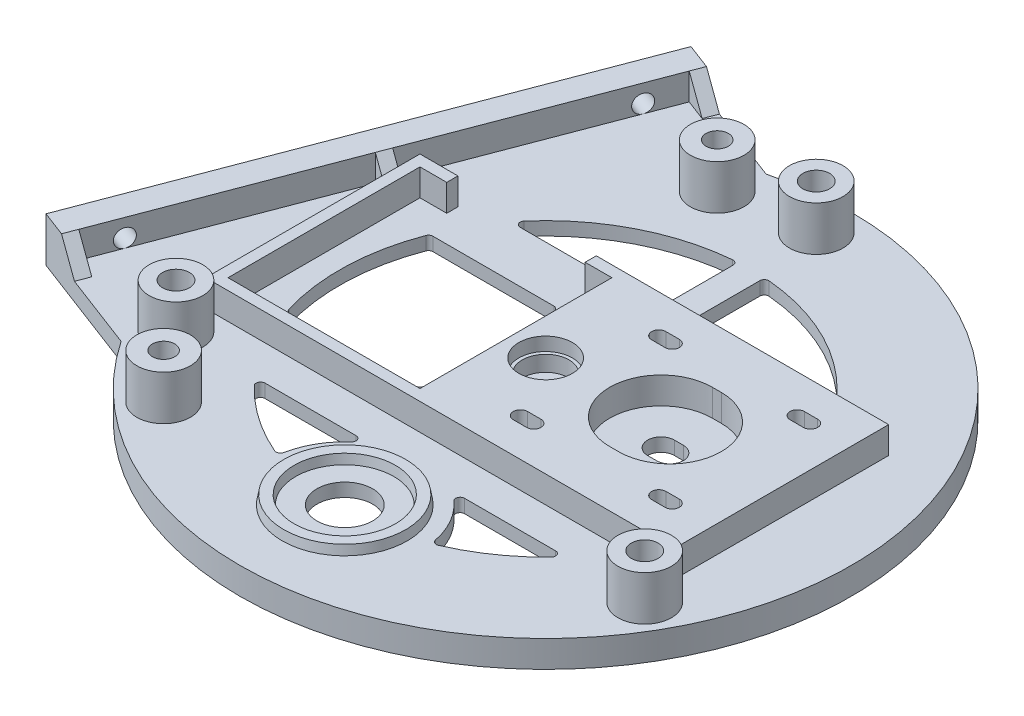
SolidWorks part; units mm, degrees
material "ABS"
ref_plane "Front Plane" through (0, 0, 0) normal (0, 0, 1) x (1, 0, 0)
ref_plane "Top Plane" through (0, 0, 0) normal (0, 1, 0) x (1, 0, 0)
ref_plane "Right Plane" through (0, 0, 0) normal (1, 0, 0) x (0, 0, -1)
sketch "Sketch1" plane through (0, 0, 0) normal (0, 0, 1) x (1, 0, 0)
  line L0 (0, 0) -> (68.5, 0)
  line L1 (68.5, 0) -> (68.5, -6)
  line L2 (68.5, -6) -> (66.5, -6)
  line L3 (66.5, -6) -> (66.5, -3)
  line L5 (53.5, -3) -> (53.5, -6)
  line L6 (53.5, -6) -> (50.5, -6)
  line L7 (50.5, -6) -> (50.5, -3)
  line L8 (50.5, -3) -> (8, -3)
  line L9 (8, -3) -> (8, -8)
  line L10 (8, -8) -> (0, -8)
  line L11 (0, -8) -> (0, 0)
  line L12 (62.3516, -3) -> (66.5, -3)
  line L13 (57.6484, -3) -> (53.5, -3)
  arc A0 (62.3516, -3) -> (57.6484, -3) centre (60, -6.6) ccw
  point P4 (67.5, -6)
  dimension "D2" = 4.3
  dimension "D1" = 60
  dimension "D3" = 6.5
  dimension "D4" = 3
  dimension "D5" = 6.5
  dimension "D6" = 3
  dimension "D7" = 2
  dimension "D8" = 50.5
  dimension "D9" = 0.6
  dimension "D10" = 8
  dimension "D11" = 8
revolve "Revolve1" add sketch "Sketch1" angle 360 about L11
sketch "Sketch2" plane through (0, 0, 0) normal (0, 1, 0) x (1, 0, 0)
  line L0 (-52.5, -30.3109) -> (0, 60.6218) construction
  line L1 (0, 60.6218) -> (52.5, -30.3109) construction
  line L2 (52.5, -30.3109) -> (-52.5, -30.3109) construction
  line L3 (0, 0) -> (0, 60.6218) construction
  line L4 (0, 0) -> (52.5, -30.3109) construction
  line L5 (0, 0) -> (-52.5, -30.3109) construction
  line L6 (0, 0) -> (0, -45) construction
  line L7 (-40.2731, -45.3109) -> (-40.2731, -30.3109) construction
  line L8 (-19.1038, 57.533) -> (-6.1134, 50.033) construction
  circle A0 centre (0, 60.6218) radius 6
  circle A1 centre (0, 60.6218) radius 3
  circle A2 centre (52.5, -30.3109) radius 6
  circle A3 centre (-52.5, -30.3109) radius 6
  circle A4 centre (-52.5, -30.3109) radius 3
  circle A5 centre (52.5, -30.3109) radius 3
  circle A6 centre (0, -45) radius 6.25 construction
  arc A7 (0, 60.6218) -> (-24.7136, -55.3555) centre (0, 0) ccw construction
  circle A8 centre (-40.2731, -45.3109) radius 6
  circle A9 centre (-19.1038, 57.533) radius 6
  circle A10 centre (-40.2731, -45.3109) radius 2.5
  circle A11 centre (-19.1038, 57.533) radius 2.5
  arc A12 (15.6635, -19.9954) -> (14.3368, 20.9671) centre (0, 0) ccw construction
  dimension "D2" = 12
  dimension "D3" = 6
  dimension "D5" = 12.5
  dimension "D6" = 12
  dimension "D8" = 5
  dimension "D9" = 25.4
  dimension "D1" = 105
  dimension "D4" = 45
  dimension "D7" = 15
extrude "Boss-Extrude1" add sketch "Sketch2" along normal blind 10
sketch "Sketch3" plane through (0, 0, 0) normal (0, 1, 0) x (1, 0, 0)
  circle A0 centre (0, -45) radius 6.25
  circle A1 centre (0, -45) radius 6.25 construction
extrude "Cut-Extrude1" cut sketch "Sketch3" against normal blind 10
sketch "Sketch12" plane through (0, 0, 0) normal (0, 1, 0) x (1, 0, 0)
  line L0 (0, 60.6218) -> (-40.2731, -45.3109) construction
  line L1 (-56.7747, -38.326) -> (-83.9292, -28.0025)
  line L2 (-83.9292, -28.0025) -> (-44.1287, 76.6871)
  line L3 (-44.1287, 76.6871) -> (-16.9742, 66.3636)
  line L4 (0, 0) -> (-64.0289, 24.3423) construction
  circle A0 centre (0, 0) radius 68.5 construction
  arc A1 (-56.7747, -38.326) -> (-16.9742, 66.3636) centre (0, 0) cw
  point P8 (-20.1366, 7.6554)
  dimension "D2" = 68.5
  dimension "D1" = 112
extrude "Boss-Extrude5" add sketch "Sketch12" against normal blind 4 contours L2 A1 L3 | L1 A1 L2 region at (-41.1369, 0, -61.2808) region at (-71.4581, 0, 18.4748)
sketch "Sketch4" plane through (0, 0, 0) normal (0, 1, 0) x (1, 0, 0)
  circle A0 centre (0, -45) radius 11
  circle A1 centre (0, -45) radius 14
  dimension "D1" = 22
  dimension "D2" = 28
extrude "Boss-Extrude2" add sketch "Sketch4" along normal blind 2 draft 10
sketch "Sketch5" plane through (0, 0, 0) normal (0, 1, 0) x (1, 0, 0)
  line L0 (51.3563, -22.5103) -> (51.3563, 25.4897)
  line L1 (51.3563, -22.5103) -> (-53.6437, -22.5103)
  line L2 (51.3563, 25.4897) -> (-53.6437, 25.4897) construction
  line L3 (-53.6437, -22.5103) -> (-53.6437, 25.4897)
  line L4 (-51.1437, 22.9897) -> (-45.1437, 22.9897)
  line L5 (-53.6437, 1.4897) -> (51.3563, 1.4897) construction
  line L6 (25.3563, 1.4897) -> (25.3563, 25.4897) construction
  line L7 (26.3563, 1.4897) -> (24.3563, 1.4897) construction
  line L8 (26.3563, -10.0103) -> (24.3563, -10.0103)
  line L9 (26.3563, 12.9897) -> (24.3563, 12.9897)
  line L10 (-45.1437, 22.9897) -> (-45.1437, 25.4897)
  line L11 (-51.1437, -20.0103) -> (-51.1437, 22.9897)
  line L12 (-51.1437, 22.9897) -> (-8.1437, 22.9897) construction
  line L13 (-8.1437, 22.9897) -> (-8.1437, -20.0103)
  line L14 (-8.1437, -20.0103) -> (-51.1437, -20.0103)
  line L15 (-45.1437, 25.4897) -> (-53.6437, 25.4897)
  line L16 (-8.1437, 22.9897) -> (-14.1437, 22.9897)
  line L17 (-14.1437, 22.9897) -> (-14.1437, 25.4897)
  line L18 (-14.1437, 25.4897) -> (51.3563, 25.4897)
  line L19 (-38.5203, 74.5549) -> (-78.3208, -30.1347)
  line L20 (-44.1287, 76.6871) -> (-16.9742, 66.3636) construction
  line L21 (-56.7747, -38.326) -> (-83.9292, -28.0025) construction
  line L22 (-78.3208, -30.1347) -> (-83.9292, -28.0025)
  line L23 (-83.9292, -28.0025) -> (-44.1287, 76.6871)
  line L24 (-83.9292, -28.0025) -> (-44.1287, 76.6871) construction
  line L25 (-44.1287, 76.6871) -> (-38.5203, 74.5549)
  arc A1 (26.3563, -10.0103) -> (26.3563, 12.9897) centre (26.3563, 1.4897) ccw
  arc A2 (24.3563, 12.9897) -> (24.3563, -10.0103) centre (24.3563, 1.4897) ccw
  arc A3 (15.6635, -19.9954) -> (14.3368, 20.9671) centre (0, 0) ccw construction
  point P10 (25.3563, 1.4897)
  point P18 (-8.1437, 1.4897)
  dimension "D3" = 23
  dimension "D1" = 48
  dimension "D2" = 105
  dimension "D4" = 2
  dimension "D5" = 26
  dimension "D6" = 2.5
  dimension "D7" = 43
  dimension "D8" = 43
  dimension "D9" = 6
  dimension "D10" = 6
  dimension "D11" = 6
extrude "Boss-Extrude3" add sketch "Sketch5" along normal blind 6
sketch "Sketch6" plane through (0, 6, 0) normal (0, 1, 0) x (1, 0, 0)
  line L0 (40.8563, -14.0103) -> (40.8563, 16.9897) construction
  line L1 (40.8563, -14.0103) -> (9.8563, -14.0103) construction
  line L2 (40.8563, 16.9897) -> (9.8563, 16.9897) construction
  line L3 (9.8563, -14.0103) -> (9.8563, 16.9897) construction
  line L4 (40.8563, -14.0103) -> (9.8563, 16.9897) construction
  line L5 (40.8563, 16.9897) -> (9.8563, -14.0103) construction
  line L6 (25.3563, 1.4897) -> (25.3563, 25.4897) construction
  line L7 (11.3563, -14.0103) -> (8.3563, -14.0103) construction
  line L8 (11.3563, -15.6103) -> (8.3563, -15.6103)
  line L9 (11.3563, -12.4103) -> (8.3563, -12.4103)
  line L10 (42.3563, -14.0103) -> (39.3563, -14.0103) construction
  line L11 (42.3563, -15.6103) -> (39.3563, -15.6103)
  line L12 (42.3563, -12.4103) -> (39.3563, -12.4103)
  line L13 (42.3563, 16.9897) -> (39.3563, 16.9897) construction
  line L14 (42.3563, 15.3897) -> (39.3563, 15.3897)
  line L15 (42.3563, 18.5897) -> (39.3563, 18.5897)
  line L16 (11.3563, 16.9897) -> (8.3563, 16.9897) construction
  line L17 (11.3563, 15.3897) -> (8.3563, 15.3897)
  line L18 (11.3563, 18.5897) -> (8.3563, 18.5897)
  arc A0 (11.3563, -15.6103) -> (11.3563, -12.4103) centre (11.3563, -14.0103) ccw
  arc A1 (8.3563, -12.4103) -> (8.3563, -15.6103) centre (8.3563, -14.0103) ccw
  arc A2 (42.3563, -15.6103) -> (42.3563, -12.4103) centre (42.3563, -14.0103) ccw
  arc A3 (39.3563, -12.4103) -> (39.3563, -15.6103) centre (39.3563, -14.0103) ccw
  arc A4 (42.3563, 15.3897) -> (42.3563, 18.5897) centre (42.3563, 16.9897) ccw
  arc A5 (39.3563, 18.5897) -> (39.3563, 15.3897) centre (39.3563, 16.9897) ccw
  arc A6 (11.3563, 15.3897) -> (11.3563, 18.5897) centre (11.3563, 16.9897) ccw
  arc A7 (8.3563, 18.5897) -> (8.3563, 15.3897) centre (8.3563, 16.9897) ccw
  point P1 (25.3563, 1.4897)
  point P2 (25.3563, 16.9897)
  point P11 (9.8563, -14.0103)
  point P21 (40.8563, -14.0103)
  point P28 (40.8563, 16.9897)
  point P35 (9.8563, 16.9897)
  dimension "D2" = 1.6
  dimension "D1" = 31
  dimension "D3" = 3
  dimension "D4" = 2
  dimension "D5" = 2
extrude "Cut-Extrude2" cut sketch "Sketch6" against normal through all
sketch "Sketch7" plane through (0, 0, 0) normal (0, 1, 0) x (1, 0, 0)
  line L0 (26.3563, 1.4897) -> (24.3563, 1.4897) construction
  line L1 (26.3563, -1.5103) -> (24.3563, -1.5103)
  line L2 (26.3563, 4.4897) -> (24.3563, 4.4897)
  arc A0 (26.3563, -1.5103) -> (26.3563, 4.4897) centre (26.3563, 1.4897) ccw
  arc A1 (24.3563, 4.4897) -> (24.3563, -1.5103) centre (24.3563, 1.4897) ccw
  point P2 (25.3563, 1.4897)
  dimension "D1" = 3
extrude "Cut-Extrude3" cut sketch "Sketch7" against normal through all
sketch "Sketch8" plane through (0, 6, 0) normal (0, 1, 0) x (1, 0, 0)
  circle A0 centre (0, 0) radius 1.75
  dimension "D1" = 3.5
extrude "Cut-Extrude4" cut sketch "Sketch8" against normal through all
chamfer "Chamfer1" distance 2 angle 45 16 edges at (37.7563, -3, 14.0103) (40.8563, -3, 12.4103) (40.8563, -3, 15.6103) (43.9563, -3, 14.0103) (37.7563, -3, -16.9897) (40.8563, -3, -18.5897) (40.8563, -3, -15.3897) (43.9563, -3, -16.9897) (6.7563, -3, -16.9897) (9.8563, -3, -18.5897) (9.8563, -3, -15.3897) (12.9563, -3, -16.9897) (6.7563, -3, 14.0103) (9.8563, -3, 12.4103) (9.8563, -3, 15.6103) (12.9563, -3, 14.0103)
sketch "Sketch9" plane through (0, 6, 0) normal (0, 1, 0) x (1, 0, 0)
  circle A0 centre (0, 0) radius 5.25
  dimension "D1" = 10.5
extrude "Cut-Extrude5" cut sketch "Sketch9" against normal blind 6.5
sketch "Sketch10" plane through (0, 6, 0) normal (0, 1, 0) x (1, 0, 0)
  circle A0 centre (0, 0) radius 6
  dimension "D1" = 12
extrude "Cut-Extrude6" cut sketch "Sketch10" against normal blind 3
sketch "Sketch11" plane through (0, 0, 0) normal (0, 1, 0) x (1, 0, 0)
  line L0 (-14.1437, -13.0103) -> (-14.1437, 15.9897)
  line L1 (-15.1437, 16.9897) -> (-42.2431, 16.9897)
  line L2 (-15.1437, -14.0103) -> (-43.2536, -14.0103)
  line L3 (-8.1437, 22.9897) -> (-8.1437, -20.0103) construction
  line L4 (-8.1437, -20.0103) -> (-51.1437, -20.0103) construction
  line L5 (-51.1437, 22.9897) -> (-8.1437, 22.9897) construction
  line L6 (-36.3293, 28.4897) -> (36.3293, 28.4897) construction
  line L7 (51.3563, 25.4897) -> (-53.6437, 25.4897) construction
  line L8 (3, 29.4897) -> (3, 44.9905)
  line L9 (-3, 29.4897) -> (-3, 44.9905)
  line L10 (-34.2126, 28.4897) -> (-4, 28.4897)
  line L11 (4, 28.4897) -> (34.2126, 28.4897)
  line L12 (52.5, -30.3109) -> (-52.5, -30.3109) construction
  line L13 (-32.5542, -30.3109) -> (-12.1463, -30.3109)
  line L14 (12.1463, -30.3109) -> (32.5542, -30.3109)
  arc A0 (-43.1783, 16.3437) -> (-44.2113, -13.2984) centre (0, 0) ccw
  arc A1 (-36.3293, 28.4897) -> (36.3293, 28.4897) centre (0, 0) cw construction
  arc A2 (-4.0886, 45.9866) -> (-34.9701, 30.1426) centre (0, 0) ccw
  arc A3 (34.9701, 30.1426) -> (4.0886, 45.9866) centre (0, 0) ccw
  arc A4 (33.2749, -32.0041) -> (18.3502, -42.3645) centre (0, 0) cw
  arc A5 (-18.3502, -42.3645) -> (-33.2749, -32.0041) centre (0, 0) cw
  arc A6 (16.9717, -41.6411) -> (11.4826, -32.0589) centre (0, -45) ccw
  arc A7 (-16.9717, -41.6411) -> (-11.4826, -32.0589) centre (0, -45) cw
  arc A8 (33.2749, -32.0041) -> (32.5542, -30.3109) centre (32.5542, -31.3109) ccw
  arc A9 (-33.2749, -32.0041) -> (-32.5542, -30.3109) centre (-32.5542, -31.3109) cw
  arc A10 (18.3502, -42.3645) -> (16.9717, -41.6411) centre (17.9527, -41.4469) cw
  arc A11 (-18.3502, -42.3645) -> (-16.9717, -41.6411) centre (-17.9527, -41.4469) ccw
  arc A12 (11.4826, -32.0589) -> (12.1463, -30.3109) centre (12.1463, -31.3109) cw
  arc A13 (-11.4826, -32.0589) -> (-12.1463, -30.3109) centre (-12.1463, -31.3109) ccw
  arc A14 (-14.1437, -13.0103) -> (-15.1437, -14.0103) centre (-15.1437, -13.0103) cw
  arc A15 (-14.1437, 15.9897) -> (-15.1437, 16.9897) centre (-15.1437, 15.9897) ccw
  arc A16 (3, 29.4897) -> (4, 28.4897) centre (4, 29.4897) ccw
  arc A17 (-3, 29.4897) -> (-4, 28.4897) centre (-4, 29.4897) cw
  arc A18 (-43.2536, -14.0103) -> (-44.2113, -13.2984) centre (-43.2536, -13.0103) cw
  arc A19 (-42.2431, 16.9897) -> (-43.1783, 16.3437) centre (-42.2431, 15.9897) ccw
  arc A20 (34.2126, 28.4897) -> (34.9701, 30.1426) centre (34.2126, 29.4897) ccw
  arc A21 (3, 44.9905) -> (4.0886, 45.9866) centre (4, 44.9905) cw
  arc A22 (-3, 44.9905) -> (-4.0886, 45.9866) centre (-4, 44.9905) ccw
  arc A23 (-34.2126, 28.4897) -> (-34.9701, 30.1426) centre (-34.2126, 29.4897) cw
  point P37 (34.8243, -30.3109)
  point P40 (-34.8243, -30.3109)
  point P47 (9.1407, -30.3109)
  point P50 (-9.1407, -30.3109)
  point P57 (3, 28.4897)
  point P60 (-3, 28.4897)
  point P70 (3, 46.0704)
  point P73 (-3, 46.0704)
  dimension "D4" = 3
  dimension "D5" = 6
  dimension "D6" = 1
  dimension "D1" = 6
  dimension "D2" = 6
  dimension "D3" = 6
extrude "Cut-Extrude7" cut sketch "Sketch11" against normal through all
sketch "Sketch13" plane through (-64.0289, 0, -24.3423) normal (-0.9347, 0, -0.3554) x (-0.3554, 0, 0.9347)
  line L0 (0, -4) -> (-56, -4) construction
  line L1 (-56, -4) -> (-56, 6) construction
  line L2 (56, -4) -> (56, 6) construction
  circle A0 centre (-45, 2) radius 2
  circle A1 centre (45, 2) radius 2
  dimension "D4" = 4
  dimension "D1" = 6
  dimension "D2" = 11
  dimension "D3" = 11
  dimension "D5" = 90
extrude "Cut-Extrude8" cut sketch "Sketch13" against normal blind 10
sketch "Sketch15" plane through (-19.9003, 0, 52.3448) normal (-0.3554, 0, 0.9347) x (0.9347, 0, 0.3554)
  line L0 (-62.5, 6) -> (-57.5, 0)
  line L1 (-39.4493, 0) -> (-62.5, 0) construction
  line L2 (-62.5, 6) -> (-62.5, 0) construction
  dimension "D1" = 5
rib "Rib1" sketch "Sketch15" sketch "Sketch15" thickness 3 extrusion direction parallel to sketch draft on no parameters "D1"=3
pattern_linear "LPattern1" count 3 spacing 54.5 along (0.3554, 0, -0.9347) of "Rib1"
